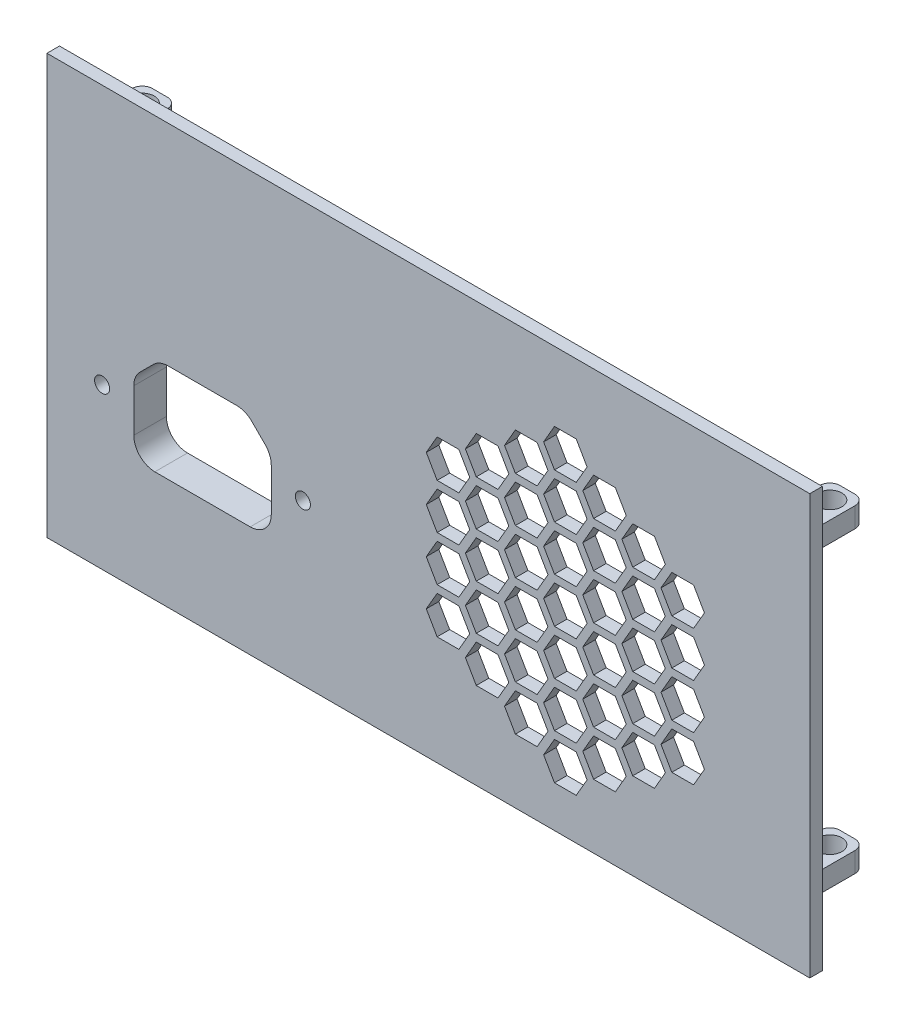
SolidWorks part; units mm, degrees
ref_plane "Front Plane" through (0, 0, 0) normal (0, 0, 1) x (1, 0, 0)
ref_plane "Top Plane" through (0, 0, 0) normal (0, 1, 0) x (1, 0, 0)
ref_plane "Right Plane" through (0, 0, 0) normal (1, 0, 0) x (0, 0, -1)
sketch "Sketch1" plane through (0, 0, 20.8372) normal (0, 0, 1) x (1, 0, 0)
  line L1 (185.4346, 13.2278) -> (33.4346, 13.2278)
  line L2 (185.4346, 13.2278) -> (185.4346, 96.8078)
  line L3 (185.4346, 96.8078) -> (33.4346, 96.8078)
  line L4 (33.4346, 13.2278) -> (33.4346, 96.8078)
extrude "Boss-Extrude1" add sketch "Sketch1" along normal blind 2.5
sketch "Sketch2" plane through (0, 0, 20.8372) normal (0, 0, -1) x (-1, 0, 0)
  line L10 (-182.9346, 15.7278) -> (-182.9346, 94.3078) construction
  line L19 (-182.6346, 25.7278) -> (-181.1346, 25.7278)
  line L20 (-182.6346, 25.7278) -> (-182.6346, 84.3078)
  line L21 (-182.6346, 84.3078) -> (-181.1346, 84.3078)
  line L22 (-181.1346, 25.7278) -> (-181.1346, 84.3078)
  line L23 (-172.9346, 94.0078) -> (-45.9346, 94.0078)
  line L24 (-172.9346, 94.0078) -> (-172.9346, 92.5078)
  line L25 (-172.9346, 92.5078) -> (-45.9346, 92.5078)
  line L26 (-45.9346, 94.0078) -> (-45.9346, 92.5078)
  line L27 (-36.2346, 84.3078) -> (-37.7346, 84.3078)
  line L28 (-36.2346, 84.3078) -> (-36.2346, 25.7278)
  line L29 (-36.2346, 25.7278) -> (-37.7346, 25.7278)
  line L30 (-37.7346, 84.3078) -> (-37.7346, 25.7278)
  line L31 (-172.9346, 16.0278) -> (-45.9346, 16.0278)
  line L32 (-172.9346, 16.0278) -> (-172.9346, 17.5278)
  line L33 (-172.9346, 17.5278) -> (-45.9346, 17.5278)
  line L34 (-45.9346, 16.0278) -> (-45.9346, 17.5278)
  line L35 (-182.9346, 94.3078) -> (-35.9346, 94.3078) construction
  line L36 (-35.9346, 94.3078) -> (-35.9346, 15.7278) construction
  line L37 (-35.9346, 15.7278) -> (-182.9346, 15.7278) construction
  dimension "D1" = 0.3
  dimension "D2" = 10
  dimension "D3" = 0.3
  dimension "D4" = 0.3
  dimension "D5" = 0.3
  dimension "D6" = 1.5
  dimension "D7" = 1.5
  dimension "D8" = 1.5
  dimension "D9" = 1.5
  dimension "D10" = 10
  dimension "D11" = 10
  dimension "D12" = 10
  dimension "D13" = 10
  dimension "D14" = 10
  dimension "D15" = 10
  dimension "D16" = 10
extrude "Boss-Extrude2" add sketch "Sketch2" along normal blind 2.5
sketch "Sketch3" plane through (0, 0, 20.8372) normal (0, 0, -1) x (-1, 0, 0)
  line L0 (-42.4346, 87.8078) -> (-39.4346, 87.8078) construction
  line L1 (-179.4346, 87.8078) -> (-176.4346, 87.8078) construction
  line L2 (-176.4346, 22.7278) -> (-179.4346, 22.7278) construction
  line L3 (-39.4346, 22.7278) -> (-42.4346, 22.7278) construction
  line L4 (-42.4346, 87.8078) -> (-39.4346, 87.8078)
  line L5 (-179.4346, 87.8078) -> (-176.4346, 87.8078)
  line L6 (-176.4346, 22.7278) -> (-179.4346, 22.7278)
  line L7 (-39.4346, 22.7278) -> (-42.4346, 22.7278)
  line L8 (-45.8096, 22.7278) -> (-35.9346, 22.7278) construction
  line L9 (-44.4346, 22.7278) -> (-37.4346, 22.7278)
  line L10 (-44.4346, 22.7278) -> (-44.4346, 26.7278)
  line L11 (-44.4346, 26.7278) -> (-37.4346, 26.7278)
  line L12 (-37.4346, 22.7278) -> (-37.4346, 26.7278)
  line L13 (-36.9346, 86.2278) -> (-181.9346, 86.2278) construction
  line L14 (-181.4346, 22.7278) -> (-174.4346, 22.7278)
  line L15 (-181.4346, 22.7278) -> (-181.4346, 26.7278)
  line L16 (-181.4346, 26.7278) -> (-174.4346, 26.7278)
  line L17 (-174.4346, 22.7278) -> (-174.4346, 26.7278)
  line L18 (-174.4346, 82.2278) -> (-181.4346, 82.2278)
  line L19 (-174.4346, 82.2278) -> (-174.4346, 86.2278)
  line L20 (-174.4346, 86.2278) -> (-181.4346, 86.2278)
  line L21 (-181.4346, 82.2278) -> (-181.4346, 86.2278)
  line L23 (-44.4346, 82.2278) -> (-37.4346, 82.2278)
  line L24 (-44.4346, 82.2278) -> (-44.4346, 86.2278)
  line L25 (-44.4346, 86.2278) -> (-37.4346, 86.2278)
  line L26 (-37.4346, 82.2278) -> (-37.4346, 86.2278)
  line M19 (-36.2346, 25.7278) -> (-37.7346, 25.7278)
  line M20 (-37.7346, 25.7278) -> (-37.7346, 84.3078)
  line M21 (-37.7346, 84.3078) -> (-36.2346, 84.3078)
  line M23 (-182.6346, 84.3078) -> (-181.1346, 84.3078)
  line M24 (-181.1346, 84.3078) -> (-181.1346, 25.7278)
  dimension "D1" = 2
  dimension "D2" = 2
  dimension "D3" = 4
  dimension "D4" = 2
  dimension "D5" = 2
  dimension "D6" = 4
  dimension "D7" = 0
  dimension "D8" = 2
  dimension "D9" = 2
  dimension "D10" = 4
  dimension "D11" = 0
  dimension "D12" = 2
  dimension "D13" = 2
  dimension "D14" = 4
extrude "Boss-Extrude3" add sketch "Sketch3" along normal blind 12.5 contours L26 L25 L24 L23 M21 M20 | L9 L12 L11 L10 L7 M19 M20 | L21 L18 L19 L20 M23 M24 | L21 L18 M24 M23 | L23 L26 M21 M20 | L12 L11 M19 M20 | L16 L17 L14 L15 region at (181.2846, 83.2678, 20.8372) region at (177.8582, 84.2497, 20.8372) region at (41.0109, 84.2497, 20.8372) region at (37.5846, 83.2678, 20.8372) region at (40.9709, 24.7116, 20.8372) region at (37.5846, 26.2278, 20.8372)
sketch "Sketch4" plane through (0, 26.7278, 0) normal (0, 1, 0) x (1, 0, 0)
  circle A0 centre (177.9346, -11.8372) radius 2.875 construction
  circle A1 centre (40.9346, -11.8372) radius 2.875 construction
  circle A2 centre (177.9346, -11.8372) radius 2.875 construction
  circle A3 centre (40.9346, -11.8372) radius 2.875 construction
  circle A4 centre (177.9346, -11.8372) radius 2.4
  circle A6 centre (40.9346, -11.8372) radius 2.4
  dimension "D1" = 4.8
  dimension "D2" = 4.8
extrude "Cut-Extrude1" cut sketch "Sketch4" against normal up to surface (4 mm away) up to face at (40.9346, 22.7278, 14.5872)
fillet "Fillet1" radius 2 8 edges at (37.4346, 24.7278, 8.3372) (44.4346, 24.7278, 8.3372) (44.4346, 84.2278, 8.3372) (37.4346, 84.2278, 8.3372) (181.4346, 84.2278, 8.3372) (174.4346, 84.2278, 8.3372) (181.4346, 24.7278, 8.3372) (174.4346, 24.7278, 8.3372)
fillet "Fillet2" radius 1 12 edges at (41.0846, 26.7278, 20.8372) (37.4346, 24.2278, 20.8372) (44.4346, 24.7278, 20.8372) (41.0846, 82.2278, 20.8372) (44.4346, 84.2278, 20.8372) (37.4346, 85.2678, 20.8372) (181.4346, 85.2678, 20.8372) (174.4346, 84.2278, 20.8372) (177.7846, 82.2278, 20.8372) (174.4346, 24.7278, 20.8372) (177.7846, 26.7278, 20.8372) (181.4346, 24.2278, 20.8372)
sketch "Sketch5" plane through (0, 82.2278, 0) normal (0, -1, 0) x (1, 0, 0)
  circle A0 centre (40.9346, 11.8372) radius 2.875 construction
  circle A1 centre (177.9346, 11.8372) radius 2.875 construction
  circle A2 centre (40.9346, 11.8372) radius 2.875 construction
  circle A3 centre (177.9346, 11.8372) radius 2.875 construction
  circle A4 centre (40.9346, 11.8372) radius 2.4
  circle A5 centre (177.9346, 11.8372) radius 2.4
  dimension "D1" = 4.8
  dimension "D2" = 4.8
extrude "Cut-Extrude2" cut sketch "Sketch5" against normal up to surface (4 mm away) up to face at (40.9346, 86.2278, 14.7854)
sketch "Sketch6" plane through (0, 0, 20.8372) normal (0, 0, -1) x (-1, 0, 0)
  line L0 (-50.7346, 39.5278) -> (-50.7346, 48.0709)
  line L1 (-51.9647, 51.0408) -> (-54.6216, 53.6976)
  line L2 (-57.5914, 54.9278) -> (-71.2777, 54.9278)
  line L3 (-74.2476, 53.6976) -> (-76.9044, 51.0408)
  line L4 (-78.1346, 48.0709) -> (-78.1346, 39.5278)
  line L5 (-73.9346, 35.3278) -> (-54.9346, 35.3278)
  line L6 (-77.9346, 48.0709) -> (-77.9346, 39.5278)
  line L7 (-73.9346, 35.5278) -> (-54.9346, 35.5278)
  line L8 (-50.9346, 39.5278) -> (-50.9346, 48.0709)
  line L9 (-52.1061, 50.8994) -> (-54.763, 53.5562)
  line L10 (-57.5914, 54.7278) -> (-71.2777, 54.7278)
  line L11 (-74.1061, 53.5562) -> (-76.763, 50.8994)
  line L12 (-77.9346, 48.0709) -> (-77.9346, 39.5278)
  line L13 (-73.9346, 35.5278) -> (-54.9346, 35.5278)
  line L14 (-50.9346, 39.5278) -> (-50.9346, 48.0709)
  line L15 (-52.1061, 50.8994) -> (-54.763, 53.5562)
  line L16 (-57.5914, 54.7278) -> (-71.2777, 54.7278)
  line L17 (-74.1061, 53.5562) -> (-76.763, 50.8994)
  line L18 (-48.7346, 39.5278) -> (-48.7346, 48.0709)
  line L19 (-50.5505, 52.455) -> (-53.2074, 55.1119)
  line L20 (-57.5914, 56.9278) -> (-71.2777, 56.9278)
  line L21 (-75.6618, 55.1119) -> (-78.3186, 52.455)
  line L22 (-80.1346, 48.0709) -> (-80.1346, 39.5278)
  line L23 (-73.9346, 33.3278) -> (-54.9346, 33.3278)
  arc A0 (-54.9346, 35.3278) -> (-50.7346, 39.5278) centre (-54.9346, 39.5278) ccw
  arc A1 (-50.7346, 48.0709) -> (-51.9647, 51.0408) centre (-54.9346, 48.0709) ccw
  arc A2 (-54.6216, 53.6976) -> (-57.5914, 54.9278) centre (-57.5914, 50.7278) ccw
  arc A3 (-71.2777, 54.9278) -> (-74.2476, 53.6976) centre (-71.2777, 50.7278) ccw
  arc A4 (-76.9044, 51.0408) -> (-78.1346, 48.0709) centre (-73.9346, 48.0709) ccw
  arc A5 (-78.1346, 39.5278) -> (-73.9346, 35.3278) centre (-73.9346, 39.5278) ccw
  arc A6 (-76.763, 50.8994) -> (-77.9346, 48.0709) centre (-73.9346, 48.0709) ccw
  arc A7 (-77.9346, 39.5278) -> (-73.9346, 35.5278) centre (-73.9346, 39.5278) ccw
  arc A8 (-54.9346, 35.5278) -> (-50.9346, 39.5278) centre (-54.9346, 39.5278) ccw
  arc A9 (-50.9346, 48.0709) -> (-52.1061, 50.8994) centre (-54.9346, 48.0709) ccw
  arc A10 (-54.763, 53.5562) -> (-57.5914, 54.7278) centre (-57.5914, 50.7278) ccw
  arc A11 (-71.2777, 54.7278) -> (-74.1061, 53.5562) centre (-71.2777, 50.7278) ccw
  arc A12 (-76.763, 50.8994) -> (-77.9346, 48.0709) centre (-73.9346, 48.0709) ccw
  arc A13 (-77.9346, 39.5278) -> (-73.9346, 35.5278) centre (-73.9346, 39.5278) ccw
  arc A14 (-54.9346, 35.5278) -> (-50.9346, 39.5278) centre (-54.9346, 39.5278) ccw
  arc A15 (-50.9346, 48.0709) -> (-52.1061, 50.8994) centre (-54.9346, 48.0709) ccw
  arc A16 (-54.763, 53.5562) -> (-57.5914, 54.7278) centre (-57.5914, 50.7278) ccw
  arc A17 (-71.2777, 54.7278) -> (-74.1061, 53.5562) centre (-71.2777, 50.7278) ccw
  arc A18 (-54.9346, 33.3278) -> (-48.7346, 39.5278) centre (-54.9346, 39.5278) ccw
  arc A19 (-48.7346, 48.0709) -> (-50.5505, 52.455) centre (-54.9346, 48.0709) ccw
  arc A20 (-53.2074, 55.1119) -> (-57.5914, 56.9278) centre (-57.5914, 50.7278) ccw
  arc A21 (-71.2777, 56.9278) -> (-75.6618, 55.1119) centre (-71.2777, 50.7278) ccw
  arc A22 (-78.3186, 52.455) -> (-80.1346, 48.0709) centre (-73.9346, 48.0709) ccw
  arc A23 (-80.1346, 39.5278) -> (-73.9346, 33.3278) centre (-73.9346, 39.5278) ccw
  dimension "D1" = 0
  dimension "D2" = 0.2
  dimension "D3" = 2
extrude "Boss-Extrude4" add sketch "Sketch6" along normal blind 4 contours L22 A23 L23 A18 L18 A19 L19 A20 L20 A21 L21 A22 A5 L4 A4 L3 A3 L2 A2 L1 A1 L0 A0 L5 region at (50.8283, 35.4215, 20.8372)
extrude "Cut-Extrude3" cut sketch "Sketch6<3>" against normal blind 5 contours L16 A17 L17 A12 L12 A13 L13 A14 L14 A15 L15 A16 | L4 A5 L5 A0 L0 A1 L1 A2 L2 A3 L3 A4 A17 L16 A16 L15 A15 L14 A14 L13 A13 L12 A12 L17 region at (51.9885, 36.5818, 20.8372) region at (64.4346, 44.8226, 20.8372)
sketch "Sketch6<3>" plane through (0, 0, 20.8372) normal (0, 0, -1) x (-1, 0, 0) same geometry as "Sketch6"
sketch "Sketch7" plane through (0, 0, 23.3372) normal (0, 0, 1) x (1, 0, 0)
  circle A0 centre (84.4346, 45.1278) radius 1.7 construction
  circle A1 centre (44.4346, 45.1278) radius 1.7 construction
  circle A2 centre (84.4346, 45.1278) radius 1.7 construction
  circle A3 centre (44.4346, 45.1278) radius 1.7 construction
  circle A4 centre (44.4346, 45.1278) radius 1.5
  circle A5 centre (84.4346, 45.1278) radius 1.5
  dimension "D1" = 3
  dimension "D2" = 3
extrude "Cut-Extrude4" cut sketch "Sketch7" against normal blind 5
sketch "Sketch8" plane through (0, 0, 23.3372) normal (0, 0, 1) x (1, 0, 0)
  line L0 (104.1177, 82.2278) -> (169.348, 22.2278) construction
  line L1 (33.4346, 13.2278) -> (185.4346, 13.2278) construction
  line L2 (165.7448, 21.4778) -> (170.0749, 21.4778)
  line L3 (170.0749, 21.4778) -> (172.24, 25.2278)
  line L4 (104.1177, 82.2278) -> (104.1177, 22.2278)
  line L5 (104.1177, 22.2278) -> (169.348, 22.2278)
  line L6 (169.348, 22.2278) -> (169.348, 82.2278)
  line L7 (169.348, 82.2278) -> (104.1177, 82.2278)
  line L8 (104.1177, 82.2278) -> (104.1177, 22.2278) construction
  line L9 (104.1177, 22.2278) -> (169.348, 22.2278) construction
  line L10 (169.348, 22.2278) -> (169.348, 82.2278) construction
  line L11 (169.348, 82.2278) -> (104.1177, 82.2278) construction
  line L12 (172.24, 25.2278) -> (170.0749, 28.9778)
  line L13 (170.0749, 28.9778) -> (165.7448, 28.9778)
  line L14 (165.7448, 28.9778) -> (163.5797, 25.2278)
  line L15 (163.5797, 25.2278) -> (165.7448, 21.4778)
  line L16 (160.1156, 29.7278) -> (167.9098, 25.2278) construction
  line L17 (157.9505, 25.9778) -> (162.2807, 25.9778)
  line L18 (162.2807, 25.9778) -> (164.4457, 29.7278)
  line L19 (164.4457, 29.7278) -> (162.2807, 33.4778)
  line L20 (162.2807, 33.4778) -> (157.9505, 33.4778)
  line L21 (157.9505, 33.4778) -> (155.7855, 29.7278)
  line L22 (155.7855, 29.7278) -> (157.9505, 25.9778)
  line L23 (150.1563, 21.4778) -> (154.4864, 21.4778)
  line L24 (154.4864, 21.4778) -> (156.6515, 25.2278)
  line L25 (156.6515, 25.2278) -> (154.4864, 28.9778)
  line L26 (154.4864, 28.9778) -> (150.1563, 28.9778)
  line L27 (150.1563, 28.9778) -> (147.9912, 25.2278)
  line L28 (147.9912, 25.2278) -> (150.1563, 21.4778)
  line L29 (142.362, 25.9778) -> (146.6922, 25.9778)
  line L30 (146.6922, 25.9778) -> (148.8572, 29.7278)
  line L31 (148.8572, 29.7278) -> (146.6922, 33.4778)
  line L32 (146.6922, 33.4778) -> (142.362, 33.4778)
  line L33 (142.362, 33.4778) -> (140.197, 29.7278)
  line L34 (140.197, 29.7278) -> (142.362, 25.9778)
  line L35 (134.5678, 21.4778) -> (138.8979, 21.4778)
  line L36 (138.8979, 21.4778) -> (141.063, 25.2278)
  line L37 (141.063, 25.2278) -> (138.8979, 28.9778)
  line L38 (138.8979, 28.9778) -> (134.5678, 28.9778)
  line L39 (134.5678, 28.9778) -> (132.4027, 25.2278)
  line L40 (132.4027, 25.2278) -> (134.5678, 21.4778)
  line L41 (126.7735, 25.9778) -> (131.1037, 25.9778)
  line L42 (131.1037, 25.9778) -> (133.2687, 29.7278)
  line L43 (133.2687, 29.7278) -> (131.1037, 33.4778)
  line L44 (131.1037, 33.4778) -> (126.7735, 33.4778)
  line L45 (126.7735, 33.4778) -> (124.6085, 29.7278)
  line L46 (124.6085, 29.7278) -> (126.7735, 25.9778)
  line L47 (118.9793, 21.4778) -> (123.3094, 21.4778)
  line L48 (123.3094, 21.4778) -> (125.4745, 25.2278)
  line L49 (125.4745, 25.2278) -> (123.3094, 28.9778)
  line L50 (123.3094, 28.9778) -> (118.9793, 28.9778)
  line L51 (118.9793, 28.9778) -> (116.8142, 25.2278)
  line L52 (116.8142, 25.2278) -> (118.9793, 21.4778)
  line L53 (111.185, 25.9778) -> (115.5152, 25.9778)
  line L54 (115.5152, 25.9778) -> (117.6802, 29.7278)
  line L55 (117.6802, 29.7278) -> (115.5152, 33.4778)
  line L56 (115.5152, 33.4778) -> (111.185, 33.4778)
  line L57 (111.185, 33.4778) -> (109.02, 29.7278)
  line L58 (109.02, 29.7278) -> (111.185, 25.9778)
  line L59 (103.3908, 21.4778) -> (107.7209, 21.4778)
  line L60 (107.7209, 21.4778) -> (109.886, 25.2278)
  line L61 (109.886, 25.2278) -> (107.7209, 28.9778)
  line L62 (107.7209, 28.9778) -> (103.3908, 28.9778)
  line L63 (103.3908, 28.9778) -> (101.2257, 25.2278)
  line L64 (101.2257, 25.2278) -> (103.3908, 21.4778)
  line L65 (95.5965, 25.9778) -> (99.9267, 25.9778)
  line L66 (99.9267, 25.9778) -> (102.0917, 29.7278)
  line L67 (102.0917, 29.7278) -> (99.9267, 33.4778)
  line L68 (99.9267, 33.4778) -> (95.5965, 33.4778)
  line L69 (95.5965, 33.4778) -> (93.4315, 29.7278)
  line L70 (93.4315, 29.7278) -> (95.5965, 25.9778)
  line L71 (150.1563, 30.4778) -> (154.4864, 30.4778)
  line L72 (154.4864, 30.4778) -> (156.6515, 34.2278)
  line L73 (156.6515, 34.2278) -> (154.4864, 37.9778)
  line L74 (154.4864, 37.9778) -> (150.1563, 37.9778)
  line L75 (150.1563, 37.9778) -> (147.9912, 34.2278)
  line L76 (147.9912, 34.2278) -> (150.1563, 30.4778)
  line L77 (142.362, 34.9778) -> (146.6922, 34.9778)
  line L78 (146.6922, 34.9778) -> (148.8572, 38.7278)
  line L79 (148.8572, 38.7278) -> (146.6922, 42.4778)
  line L80 (146.6922, 42.4778) -> (142.362, 42.4778)
  line L81 (142.362, 42.4778) -> (140.197, 38.7278)
  line L82 (140.197, 38.7278) -> (142.362, 34.9778)
  line L83 (134.5678, 30.4778) -> (138.8979, 30.4778)
  line L84 (138.8979, 30.4778) -> (141.063, 34.2278)
  line L85 (141.063, 34.2278) -> (138.8979, 37.9778)
  line L86 (138.8979, 37.9778) -> (134.5678, 37.9778)
  line L87 (134.5678, 37.9778) -> (132.4027, 34.2278)
  line L88 (132.4027, 34.2278) -> (134.5678, 30.4778)
  line L89 (126.7735, 34.9778) -> (131.1037, 34.9778)
  line L90 (131.1037, 34.9778) -> (133.2687, 38.7278)
  line L91 (133.2687, 38.7278) -> (131.1037, 42.4778)
  line L92 (131.1037, 42.4778) -> (126.7735, 42.4778)
  line L93 (126.7735, 42.4778) -> (124.6085, 38.7278)
  line L94 (124.6085, 38.7278) -> (126.7735, 34.9778)
  line L95 (118.9793, 30.4778) -> (123.3094, 30.4778)
  line L96 (123.3094, 30.4778) -> (125.4745, 34.2278)
  line L97 (125.4745, 34.2278) -> (123.3094, 37.9778)
  line L98 (123.3094, 37.9778) -> (118.9793, 37.9778)
  line L99 (118.9793, 37.9778) -> (116.8142, 34.2278)
  line L100 (116.8142, 34.2278) -> (118.9793, 30.4778)
  line L101 (111.185, 34.9778) -> (115.5152, 34.9778)
  line L102 (115.5152, 34.9778) -> (117.6802, 38.7278)
  line L103 (117.6802, 38.7278) -> (115.5152, 42.4778)
  line L104 (115.5152, 42.4778) -> (111.185, 42.4778)
  line L105 (111.185, 42.4778) -> (109.02, 38.7278)
  line L106 (109.02, 38.7278) -> (111.185, 34.9778)
  line L107 (103.3908, 30.4778) -> (107.7209, 30.4778)
  line L108 (107.7209, 30.4778) -> (109.886, 34.2278)
  line L109 (109.886, 34.2278) -> (107.7209, 37.9778)
  line L110 (107.7209, 37.9778) -> (103.3908, 37.9778)
  line L111 (103.3908, 37.9778) -> (101.2257, 34.2278)
  line L112 (101.2257, 34.2278) -> (103.3908, 30.4778)
  line L113 (95.5965, 34.9778) -> (99.9267, 34.9778)
  line L114 (99.9267, 34.9778) -> (102.0917, 38.7278)
  line L115 (102.0917, 38.7278) -> (99.9267, 42.4778)
  line L116 (99.9267, 42.4778) -> (95.5965, 42.4778)
  line L117 (95.5965, 42.4778) -> (93.4315, 38.7278)
  line L118 (93.4315, 38.7278) -> (95.5965, 34.9778)
  line L119 (150.1563, 39.4778) -> (154.4864, 39.4778)
  line L120 (154.4864, 39.4778) -> (156.6515, 43.2278)
  line L121 (156.6515, 43.2278) -> (154.4864, 46.9778)
  line L122 (154.4864, 46.9778) -> (150.1563, 46.9778)
  line L123 (150.1563, 46.9778) -> (147.9912, 43.2278)
  line L124 (147.9912, 43.2278) -> (150.1563, 39.4778)
  line L125 (142.362, 43.9778) -> (146.6922, 43.9778)
  line L126 (146.6922, 43.9778) -> (148.8572, 47.7278)
  line L127 (148.8572, 47.7278) -> (146.6922, 51.4778)
  line L128 (146.6922, 51.4778) -> (142.362, 51.4778)
  line L129 (142.362, 51.4778) -> (140.197, 47.7278)
  line L130 (140.197, 47.7278) -> (142.362, 43.9778)
  line L131 (134.5678, 39.4778) -> (138.8979, 39.4778)
  line L132 (138.8979, 39.4778) -> (141.063, 43.2278)
  line L133 (141.063, 43.2278) -> (138.8979, 46.9778)
  line L134 (138.8979, 46.9778) -> (134.5678, 46.9778)
  line L135 (134.5678, 46.9778) -> (132.4027, 43.2278)
  line L136 (132.4027, 43.2278) -> (134.5678, 39.4778)
  line L137 (126.7735, 43.9778) -> (131.1037, 43.9778)
  line L138 (131.1037, 43.9778) -> (133.2687, 47.7278)
  line L139 (133.2687, 47.7278) -> (131.1037, 51.4778)
  line L140 (131.1037, 51.4778) -> (126.7735, 51.4778)
  line L141 (126.7735, 51.4778) -> (124.6085, 47.7278)
  line L142 (124.6085, 47.7278) -> (126.7735, 43.9778)
  line L143 (118.9793, 39.4778) -> (123.3094, 39.4778)
  line L144 (123.3094, 39.4778) -> (125.4745, 43.2278)
  line L145 (125.4745, 43.2278) -> (123.3094, 46.9778)
  line L146 (123.3094, 46.9778) -> (118.9793, 46.9778)
  line L147 (118.9793, 46.9778) -> (116.8142, 43.2278)
  line L148 (116.8142, 43.2278) -> (118.9793, 39.4778)
  line L149 (111.185, 43.9778) -> (115.5152, 43.9778)
  line L150 (115.5152, 43.9778) -> (117.6802, 47.7278)
  line L151 (117.6802, 47.7278) -> (115.5152, 51.4778)
  line L152 (115.5152, 51.4778) -> (111.185, 51.4778)
  line L153 (111.185, 51.4778) -> (109.02, 47.7278)
  line L154 (109.02, 47.7278) -> (111.185, 43.9778)
  line L155 (103.3908, 39.4778) -> (107.7209, 39.4778)
  line L156 (107.7209, 39.4778) -> (109.886, 43.2278)
  line L157 (109.886, 43.2278) -> (107.7209, 46.9778)
  line L158 (107.7209, 46.9778) -> (103.3908, 46.9778)
  line L159 (103.3908, 46.9778) -> (101.2257, 43.2278)
  line L160 (101.2257, 43.2278) -> (103.3908, 39.4778)
  line L161 (95.5965, 43.9778) -> (99.9267, 43.9778)
  line L162 (99.9267, 43.9778) -> (102.0917, 47.7278)
  line L163 (102.0917, 47.7278) -> (99.9267, 51.4778)
  line L164 (99.9267, 51.4778) -> (95.5965, 51.4778)
  line L165 (95.5965, 51.4778) -> (93.4315, 47.7278)
  line L166 (93.4315, 47.7278) -> (95.5965, 43.9778)
  line L167 (150.1563, 48.4778) -> (154.4864, 48.4778)
  line L168 (154.4864, 48.4778) -> (156.6515, 52.2278)
  line L169 (156.6515, 52.2278) -> (154.4864, 55.9778)
  line L170 (154.4864, 55.9778) -> (150.1563, 55.9778)
  line L171 (150.1563, 55.9778) -> (147.9912, 52.2278)
  line L172 (147.9912, 52.2278) -> (150.1563, 48.4778)
  line L173 (142.362, 52.9778) -> (146.6922, 52.9778)
  line L174 (146.6922, 52.9778) -> (148.8572, 56.7278)
  line L175 (148.8572, 56.7278) -> (146.6922, 60.4778)
  line L176 (146.6922, 60.4778) -> (142.362, 60.4778)
  line L177 (142.362, 60.4778) -> (140.197, 56.7278)
  line L178 (140.197, 56.7278) -> (142.362, 52.9778)
  line L179 (134.5678, 48.4778) -> (138.8979, 48.4778)
  line L180 (138.8979, 48.4778) -> (141.063, 52.2278)
  line L181 (141.063, 52.2278) -> (138.8979, 55.9778)
  line L182 (138.8979, 55.9778) -> (134.5678, 55.9778)
  line L183 (134.5678, 55.9778) -> (132.4027, 52.2278)
  line L184 (132.4027, 52.2278) -> (134.5678, 48.4778)
  line L185 (126.7735, 52.9778) -> (131.1037, 52.9778)
  line L186 (131.1037, 52.9778) -> (133.2687, 56.7278)
  line L187 (133.2687, 56.7278) -> (131.1037, 60.4778)
  line L188 (131.1037, 60.4778) -> (126.7735, 60.4778)
  line L189 (126.7735, 60.4778) -> (124.6085, 56.7278)
  line L190 (124.6085, 56.7278) -> (126.7735, 52.9778)
  line L191 (118.9793, 48.4778) -> (123.3094, 48.4778)
  line L192 (123.3094, 48.4778) -> (125.4745, 52.2278)
  line L193 (125.4745, 52.2278) -> (123.3094, 55.9778)
  line L194 (123.3094, 55.9778) -> (118.9793, 55.9778)
  line L195 (118.9793, 55.9778) -> (116.8142, 52.2278)
  line L196 (116.8142, 52.2278) -> (118.9793, 48.4778)
  line L197 (111.185, 52.9778) -> (115.5152, 52.9778)
  line L198 (115.5152, 52.9778) -> (117.6802, 56.7278)
  line L199 (117.6802, 56.7278) -> (115.5152, 60.4778)
  line L200 (115.5152, 60.4778) -> (111.185, 60.4778)
  line L201 (111.185, 60.4778) -> (109.02, 56.7278)
  line L202 (109.02, 56.7278) -> (111.185, 52.9778)
  line L203 (103.3908, 48.4778) -> (107.7209, 48.4778)
  line L204 (107.7209, 48.4778) -> (109.886, 52.2278)
  line L205 (109.886, 52.2278) -> (107.7209, 55.9778)
  line L206 (107.7209, 55.9778) -> (103.3908, 55.9778)
  line L207 (103.3908, 55.9778) -> (101.2257, 52.2278)
  line L208 (101.2257, 52.2278) -> (103.3908, 48.4778)
  line L209 (95.5965, 52.9778) -> (99.9267, 52.9778)
  line L210 (99.9267, 52.9778) -> (102.0917, 56.7278)
  line L211 (102.0917, 56.7278) -> (99.9267, 60.4778)
  line L212 (99.9267, 60.4778) -> (95.5965, 60.4778)
  line L213 (95.5965, 60.4778) -> (93.4315, 56.7278)
  line L214 (93.4315, 56.7278) -> (95.5965, 52.9778)
  line L215 (150.1563, 57.4778) -> (154.4864, 57.4778)
  line L216 (154.4864, 57.4778) -> (156.6515, 61.2278)
  line L217 (156.6515, 61.2278) -> (154.4864, 64.9778)
  line L218 (154.4864, 64.9778) -> (150.1563, 64.9778)
  line L219 (150.1563, 64.9778) -> (147.9912, 61.2278)
  line L220 (147.9912, 61.2278) -> (150.1563, 57.4778)
  line L221 (142.362, 61.9778) -> (146.6922, 61.9778)
  line L222 (146.6922, 61.9778) -> (148.8572, 65.7278)
  line L223 (148.8572, 65.7278) -> (146.6922, 69.4778)
  line L224 (146.6922, 69.4778) -> (142.362, 69.4778)
  line L225 (142.362, 69.4778) -> (140.197, 65.7278)
  line L226 (140.197, 65.7278) -> (142.362, 61.9778)
  line L227 (134.5678, 57.4778) -> (138.8979, 57.4778)
  line L228 (138.8979, 57.4778) -> (141.063, 61.2278)
  line L229 (141.063, 61.2278) -> (138.8979, 64.9778)
  line L230 (138.8979, 64.9778) -> (134.5678, 64.9778)
  line L231 (134.5678, 64.9778) -> (132.4027, 61.2278)
  line L232 (132.4027, 61.2278) -> (134.5678, 57.4778)
  line L233 (126.7735, 61.9778) -> (131.1037, 61.9778)
  line L234 (131.1037, 61.9778) -> (133.2687, 65.7278)
  line L235 (133.2687, 65.7278) -> (131.1037, 69.4778)
  line L236 (131.1037, 69.4778) -> (126.7735, 69.4778)
  line L237 (126.7735, 69.4778) -> (124.6085, 65.7278)
  line L238 (124.6085, 65.7278) -> (126.7735, 61.9778)
  line L239 (118.9793, 57.4778) -> (123.3094, 57.4778)
  line L240 (123.3094, 57.4778) -> (125.4745, 61.2278)
  line L241 (125.4745, 61.2278) -> (123.3094, 64.9778)
  line L242 (123.3094, 64.9778) -> (118.9793, 64.9778)
  line L243 (118.9793, 64.9778) -> (116.8142, 61.2278)
  line L244 (116.8142, 61.2278) -> (118.9793, 57.4778)
  line L245 (111.185, 61.9778) -> (115.5152, 61.9778)
  line L246 (115.5152, 61.9778) -> (117.6802, 65.7278)
  line L247 (117.6802, 65.7278) -> (115.5152, 69.4778)
  line L248 (115.5152, 69.4778) -> (111.185, 69.4778)
  line L249 (111.185, 69.4778) -> (109.02, 65.7278)
  line L250 (109.02, 65.7278) -> (111.185, 61.9778)
  line L251 (103.3908, 57.4778) -> (107.7209, 57.4778)
  line L252 (107.7209, 57.4778) -> (109.886, 61.2278)
  line L253 (109.886, 61.2278) -> (107.7209, 64.9778)
  line L254 (107.7209, 64.9778) -> (103.3908, 64.9778)
  line L255 (103.3908, 64.9778) -> (101.2257, 61.2278)
  line L256 (101.2257, 61.2278) -> (103.3908, 57.4778)
  line L257 (95.5965, 61.9778) -> (99.9267, 61.9778)
  line L258 (99.9267, 61.9778) -> (102.0917, 65.7278)
  line L259 (102.0917, 65.7278) -> (99.9267, 69.4778)
  line L260 (99.9267, 69.4778) -> (95.5965, 69.4778)
  line L261 (95.5965, 69.4778) -> (93.4315, 65.7278)
  line L262 (93.4315, 65.7278) -> (95.5965, 61.9778)
  line L263 (150.1563, 66.4778) -> (154.4864, 66.4778)
  line L264 (154.4864, 66.4778) -> (156.6515, 70.2278)
  line L265 (156.6515, 70.2278) -> (154.4864, 73.9778)
  line L266 (154.4864, 73.9778) -> (150.1563, 73.9778)
  line L267 (150.1563, 73.9778) -> (147.9912, 70.2278)
  line L268 (147.9912, 70.2278) -> (150.1563, 66.4778)
  line L269 (142.362, 70.9778) -> (146.6922, 70.9778)
  line L270 (146.6922, 70.9778) -> (148.8572, 74.7278)
  line L271 (148.8572, 74.7278) -> (146.6922, 78.4778)
  line L272 (146.6922, 78.4778) -> (142.362, 78.4778)
  line L273 (142.362, 78.4778) -> (140.197, 74.7278)
  line L274 (140.197, 74.7278) -> (142.362, 70.9778)
  line L275 (134.5678, 66.4778) -> (138.8979, 66.4778)
  line L276 (138.8979, 66.4778) -> (141.063, 70.2278)
  line L277 (141.063, 70.2278) -> (138.8979, 73.9778)
  line L278 (138.8979, 73.9778) -> (134.5678, 73.9778)
  line L279 (134.5678, 73.9778) -> (132.4027, 70.2278)
  line L280 (132.4027, 70.2278) -> (134.5678, 66.4778)
  line L281 (126.7735, 70.9778) -> (131.1037, 70.9778)
  line L282 (131.1037, 70.9778) -> (133.2687, 74.7278)
  line L283 (133.2687, 74.7278) -> (131.1037, 78.4778)
  line L284 (131.1037, 78.4778) -> (126.7735, 78.4778)
  line L285 (126.7735, 78.4778) -> (124.6085, 74.7278)
  line L286 (124.6085, 74.7278) -> (126.7735, 70.9778)
  line L287 (118.9793, 66.4778) -> (123.3094, 66.4778)
  line L288 (123.3094, 66.4778) -> (125.4745, 70.2278)
  line L289 (125.4745, 70.2278) -> (123.3094, 73.9778)
  line L290 (123.3094, 73.9778) -> (118.9793, 73.9778)
  line L291 (118.9793, 73.9778) -> (116.8142, 70.2278)
  line L292 (116.8142, 70.2278) -> (118.9793, 66.4778)
  line L293 (111.185, 70.9778) -> (115.5152, 70.9778)
  line L294 (115.5152, 70.9778) -> (117.6802, 74.7278)
  line L295 (117.6802, 74.7278) -> (115.5152, 78.4778)
  line L296 (115.5152, 78.4778) -> (111.185, 78.4778)
  line L297 (111.185, 78.4778) -> (109.02, 74.7278)
  line L298 (109.02, 74.7278) -> (111.185, 70.9778)
  line L299 (103.3908, 66.4778) -> (107.7209, 66.4778)
  line L300 (107.7209, 66.4778) -> (109.886, 70.2278)
  line L301 (109.886, 70.2278) -> (107.7209, 73.9778)
  line L302 (107.7209, 73.9778) -> (103.3908, 73.9778)
  line L303 (103.3908, 73.9778) -> (101.2257, 70.2278)
  line L304 (101.2257, 70.2278) -> (103.3908, 66.4778)
  line L305 (95.5965, 70.9778) -> (99.9267, 70.9778)
  line L306 (99.9267, 70.9778) -> (102.0917, 74.7278)
  line L307 (102.0917, 74.7278) -> (99.9267, 78.4778)
  line L308 (99.9267, 78.4778) -> (95.5965, 78.4778)
  line L309 (95.5965, 78.4778) -> (93.4315, 74.7278)
  line L310 (93.4315, 74.7278) -> (95.5965, 70.9778)
  line L311 (150.1563, 75.4778) -> (154.4864, 75.4778)
  line L312 (154.4864, 75.4778) -> (156.6515, 79.2278)
  line L313 (156.6515, 79.2278) -> (154.4864, 82.9778)
  line L314 (154.4864, 82.9778) -> (150.1563, 82.9778)
  line L315 (150.1563, 82.9778) -> (147.9912, 79.2278)
  line L316 (147.9912, 79.2278) -> (150.1563, 75.4778)
  line L317 (142.362, 79.9778) -> (146.6922, 79.9778)
  line L318 (146.6922, 79.9778) -> (148.8572, 83.7278)
  line L319 (148.8572, 83.7278) -> (146.6922, 87.4778)
  line L320 (146.6922, 87.4778) -> (142.362, 87.4778)
  line L321 (142.362, 87.4778) -> (140.197, 83.7278)
  line L322 (140.197, 83.7278) -> (142.362, 79.9778)
  line L323 (134.5678, 75.4778) -> (138.8979, 75.4778)
  line L324 (138.8979, 75.4778) -> (141.063, 79.2278)
  line L325 (141.063, 79.2278) -> (138.8979, 82.9778)
  line L326 (138.8979, 82.9778) -> (134.5678, 82.9778)
  line L327 (134.5678, 82.9778) -> (132.4027, 79.2278)
  line L328 (132.4027, 79.2278) -> (134.5678, 75.4778)
  line L329 (126.7735, 79.9778) -> (131.1037, 79.9778)
  line L330 (131.1037, 79.9778) -> (133.2687, 83.7278)
  line L331 (133.2687, 83.7278) -> (131.1037, 87.4778)
  line L332 (131.1037, 87.4778) -> (126.7735, 87.4778)
  line L333 (126.7735, 87.4778) -> (124.6085, 83.7278)
  line L334 (124.6085, 83.7278) -> (126.7735, 79.9778)
  line L335 (118.9793, 75.4778) -> (123.3094, 75.4778)
  line L336 (123.3094, 75.4778) -> (125.4745, 79.2278)
  line L337 (125.4745, 79.2278) -> (123.3094, 82.9778)
  line L338 (123.3094, 82.9778) -> (118.9793, 82.9778)
  line L339 (118.9793, 82.9778) -> (116.8142, 79.2278)
  line L340 (116.8142, 79.2278) -> (118.9793, 75.4778)
  line L341 (111.185, 79.9778) -> (115.5152, 79.9778)
  line L342 (115.5152, 79.9778) -> (117.6802, 83.7278)
  line L343 (117.6802, 83.7278) -> (115.5152, 87.4778)
  line L344 (115.5152, 87.4778) -> (111.185, 87.4778)
  line L345 (111.185, 87.4778) -> (109.02, 83.7278)
  line L346 (109.02, 83.7278) -> (111.185, 79.9778)
  line L347 (103.3908, 75.4778) -> (107.7209, 75.4778)
  line L348 (107.7209, 75.4778) -> (109.886, 79.2278)
  line L349 (109.886, 79.2278) -> (107.7209, 82.9778)
  line L350 (107.7209, 82.9778) -> (103.3908, 82.9778)
  line L351 (103.3908, 82.9778) -> (101.2257, 79.2278)
  line L352 (101.2257, 79.2278) -> (103.3908, 75.4778)
  line L353 (95.5965, 79.9778) -> (99.9267, 79.9778)
  line L354 (99.9267, 79.9778) -> (102.0917, 83.7278)
  line L355 (102.0917, 83.7278) -> (99.9267, 87.4778)
  line L356 (99.9267, 87.4778) -> (95.5965, 87.4778)
  line L357 (95.5965, 87.4778) -> (93.4315, 83.7278)
  line L358 (93.4315, 83.7278) -> (95.5965, 79.9778)
  line L359 (165.7448, 30.4778) -> (170.0749, 30.4778)
  line L360 (170.0749, 30.4778) -> (172.24, 34.2278)
  line L361 (172.24, 34.2278) -> (170.0749, 37.9778)
  line L362 (170.0749, 37.9778) -> (165.7448, 37.9778)
  line L363 (165.7448, 37.9778) -> (163.5797, 34.2278)
  line L364 (163.5797, 34.2278) -> (165.7448, 30.4778)
  line L365 (157.9505, 34.9778) -> (162.2807, 34.9778)
  line L366 (162.2807, 34.9778) -> (164.4457, 38.7278)
  line L367 (164.4457, 38.7278) -> (162.2807, 42.4778)
  line L368 (162.2807, 42.4778) -> (157.9505, 42.4778)
  line L369 (157.9505, 42.4778) -> (155.7855, 38.7278)
  line L370 (155.7855, 38.7278) -> (157.9505, 34.9778)
  line L371 (165.7448, 39.4778) -> (170.0749, 39.4778)
  line L372 (170.0749, 39.4778) -> (172.24, 43.2278)
  line L373 (172.24, 43.2278) -> (170.0749, 46.9778)
  line L374 (170.0749, 46.9778) -> (165.7448, 46.9778)
  line L375 (165.7448, 46.9778) -> (163.5797, 43.2278)
  line L376 (163.5797, 43.2278) -> (165.7448, 39.4778)
  line L377 (157.9505, 43.9778) -> (162.2807, 43.9778)
  line L378 (162.2807, 43.9778) -> (164.4457, 47.7278)
  line L379 (164.4457, 47.7278) -> (162.2807, 51.4778)
  line L380 (162.2807, 51.4778) -> (157.9505, 51.4778)
  line L381 (157.9505, 51.4778) -> (155.7855, 47.7278)
  line L382 (155.7855, 47.7278) -> (157.9505, 43.9778)
  line L383 (165.7448, 48.4778) -> (170.0749, 48.4778)
  line L384 (170.0749, 48.4778) -> (172.24, 52.2278)
  line L385 (172.24, 52.2278) -> (170.0749, 55.9778)
  line L386 (170.0749, 55.9778) -> (165.7448, 55.9778)
  line L387 (165.7448, 55.9778) -> (163.5797, 52.2278)
  line L388 (163.5797, 52.2278) -> (165.7448, 48.4778)
  line L389 (157.9505, 52.9778) -> (162.2807, 52.9778)
  line L390 (162.2807, 52.9778) -> (164.4457, 56.7278)
  line L391 (164.4457, 56.7278) -> (162.2807, 60.4778)
  line L392 (162.2807, 60.4778) -> (157.9505, 60.4778)
  line L393 (157.9505, 60.4778) -> (155.7855, 56.7278)
  line L394 (155.7855, 56.7278) -> (157.9505, 52.9778)
  line L395 (165.7448, 57.4778) -> (170.0749, 57.4778)
  line L396 (170.0749, 57.4778) -> (172.24, 61.2278)
  line L397 (172.24, 61.2278) -> (170.0749, 64.9778)
  line L398 (170.0749, 64.9778) -> (165.7448, 64.9778)
  line L399 (165.7448, 64.9778) -> (163.5797, 61.2278)
  line L400 (163.5797, 61.2278) -> (165.7448, 57.4778)
  line L401 (157.9505, 61.9778) -> (162.2807, 61.9778)
  line L402 (162.2807, 61.9778) -> (164.4457, 65.7278)
  line L403 (164.4457, 65.7278) -> (162.2807, 69.4778)
  line L404 (162.2807, 69.4778) -> (157.9505, 69.4778)
  line L405 (157.9505, 69.4778) -> (155.7855, 65.7278)
  line L406 (155.7855, 65.7278) -> (157.9505, 61.9778)
  line L407 (165.7448, 66.4778) -> (170.0749, 66.4778)
  line L408 (170.0749, 66.4778) -> (172.24, 70.2278)
  line L409 (172.24, 70.2278) -> (170.0749, 73.9778)
  line L410 (170.0749, 73.9778) -> (165.7448, 73.9778)
  line L411 (165.7448, 73.9778) -> (163.5797, 70.2278)
  line L412 (163.5797, 70.2278) -> (165.7448, 66.4778)
  line L413 (157.9505, 70.9778) -> (162.2807, 70.9778)
  line L414 (162.2807, 70.9778) -> (164.4457, 74.7278)
  line L415 (164.4457, 74.7278) -> (162.2807, 78.4778)
  line L416 (162.2807, 78.4778) -> (157.9505, 78.4778)
  line L417 (157.9505, 78.4778) -> (155.7855, 74.7278)
  line L418 (155.7855, 74.7278) -> (157.9505, 70.9778)
  line L419 (165.7448, 75.4778) -> (170.0749, 75.4778)
  line L420 (170.0749, 75.4778) -> (172.24, 79.2278)
  line L421 (172.24, 79.2278) -> (170.0749, 82.9778)
  line L422 (170.0749, 82.9778) -> (165.7448, 82.9778)
  line L423 (165.7448, 82.9778) -> (163.5797, 79.2278)
  line L424 (163.5797, 79.2278) -> (165.7448, 75.4778)
  line L425 (157.9505, 79.9778) -> (162.2807, 79.9778)
  line L426 (162.2807, 79.9778) -> (164.4457, 83.7278)
  line L427 (164.4457, 83.7278) -> (162.2807, 87.4778)
  line L428 (162.2807, 87.4778) -> (157.9505, 87.4778)
  line L429 (157.9505, 87.4778) -> (155.7855, 83.7278)
  line L430 (155.7855, 83.7278) -> (157.9505, 79.9778)
  circle A0 centre (136.7328, 52.2278) radius 30 construction
  circle A1 centre (167.9098, 25.2278) radius 3.75 construction
  circle A2 centre (160.1156, 29.7278) radius 3.75 construction
  dimension "D2" = 7.5
  dimension "D3" = 7.5
  dimension "D4" = 1.5
  dimension "D5" = 31.177
  dimension "D6" = 27
  dimension "D1" = 0
  dimension "D7" = 5
  dimension "D8" = 7
extrude "Cut-Extrude5" cut sketch "Sketch8" against normal blind 3 contours L369 L370 L365 L366 L367 L368 | L75 L76 L71 L72 L73 L74 | L33 L34 L29 L30 L31 L32 | L39 L40 L35 L36 L37 L38 | L45 L46 L41 L42 L43 L44 | L99 L100 L95 L96 L97 L98 | L105 L106 L101 L102 L103 L104 | L153 L154 L149 L150 L151 L152 | L201 L202 L197 L198 L199 L200 | L249 L250 L245 L246 L247 L248 | L291 L292 L287 L288 L289 L290 | L285 L286 L281 L282 L283 L284 | L327 L328 L323 L324 L325 L326 | L273 L274 L269 L270 L271 L272 | L267 L268 L263 L264 L265 L266 | L405 L406 L401 L402 L403 L404 | L393 L394 L389 L390 L391 L392 | L381 L382 L377 L378 L379 L380 | L123 L124 L119 L120 L121 L122 | L171 L172 L167 L168 L169 L170 | L219 L220 L215 L216 L217 L218 | L225 L226 L221 L222 L223 L224 | L279 L280 L275 L276 L277 L278 | L231 L232 L227 L228 L229 L230 | L177 L178 L173 L174 L175 L176 | L129 L130 L125 L126 L127 L128 | L81 L82 L77 L78 L79 L80 | L87 L88 L83 L84 L85 L86 | L135 L136 L131 L132 L133 L134 | L183 L184 L179 L180 L181 L182 | L141 L142 L137 L138 L139 L140 | L93 L94 L89 L90 L91 L92 | L147 L148 L143 L144 L145 L146 | L195 L196 L191 L192 L193 L194 | L243 L244 L239 L240 L241 L242 | L237 L238 L233 L234 L235 L236 | L189 L190 L185 L186 L187 L188 region at (136.7328, 21.8642, 23.3372) region at (136.7328, 25.494, 23.3372) region at (136.7328, 78.9616, 23.3372) region at (136.7328, 82.5914, 23.3372) region at (144.5271, 29.7278, 23.3372) region at (128.9386, 29.7278, 23.3372) region at (152.3213, 34.2278, 23.3372) region at (144.5271, 38.7278, 23.3372) region at (136.7328, 34.2278, 23.3372) region at (128.9386, 38.7278, 23.3372) region at (121.1443, 34.2278, 23.3372) region at (113.3501, 38.7278, 23.3372) region at (152.3213, 43.2278, 23.3372) region at (144.5271, 47.7278, 23.3372) region at (136.7328, 43.2278, 23.3372) region at (128.9386, 47.7278, 23.3372) region at (121.1443, 43.2278, 23.3372) region at (113.3501, 47.7278, 23.3372) region at (152.3213, 52.2278, 23.3372) region at (144.5271, 56.7278, 23.3372) region at (136.7328, 52.2278, 23.3372) region at (128.9386, 56.7278, 23.3372) region at (121.1443, 52.2278, 23.3372) region at (113.3501, 56.7278, 23.3372) region at (152.3213, 61.2278, 23.3372) region at (144.5271, 65.7278, 23.3372) region at (136.7328, 61.2278, 23.3372) region at (128.9386, 65.7278, 23.3372) region at (121.1443, 61.2278, 23.3372) region at (113.3501, 65.7278, 23.3372) region at (152.3213, 70.2278, 23.3372) region at (144.5271, 74.7278, 23.3372) region at (136.7328, 70.2278, 23.3372) region at (128.9386, 74.7278, 23.3372) region at (121.1443, 70.2278, 23.3372) region at (160.1156, 38.7278, 23.3372) region at (160.1156, 47.7278, 23.3372) region at (160.1156, 56.7278, 23.3372) region at (160.1156, 65.7278, 23.3372)
